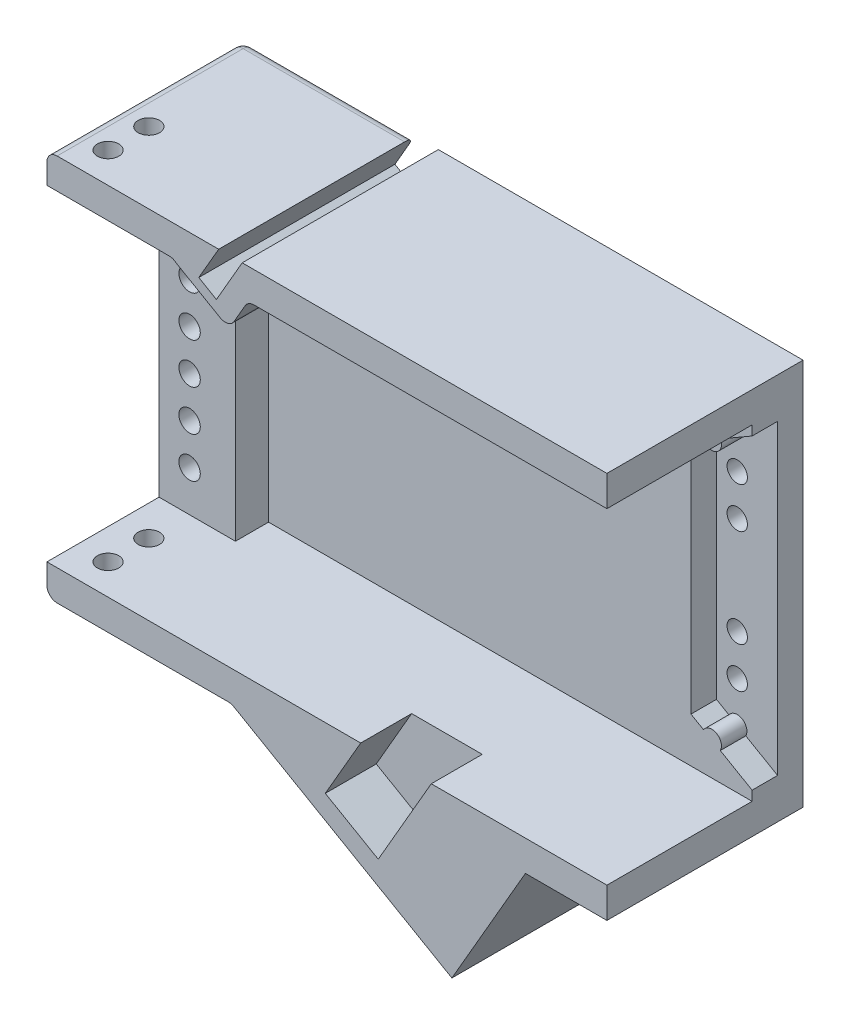
SolidWorks part; units mm, degrees
material "ABS"
ref_plane "前基準面" through (0, 0, 0) normal (0, 0, 1) x (1, 0, 0)
ref_plane "上基準面" through (0, 0, 0) normal (0, 1, 0) x (1, 0, 0)
ref_plane "右基準面" through (0, 0, 0) normal (1, 0, 0) x (0, 0, -1)
sketch "草圖2" plane through (0, 0, 0) normal (0, 0, 1) x (1, 0, 0)
  line L1 (-42.4346, 62.0442) -> (67.4854, 62.0442)
  line L2 (-42.4346, 62.0442) -> (-42.4346, -13.9558)
  line L3 (-42.4346, -13.9558) -> (67.4854, -13.9558)
  line L4 (67.4854, 62.0442) -> (67.4854, -13.9558)
  dimension "D1" = 109.92
  dimension "D2" = 76
extrude "填料-伸長1" add sketch "草圖2" along normal blind 10
sketch "草圖3" plane through (0, 0, 10) normal (0, 0, 1) x (1, 0, 0)
  line L0 (67.4854, 54.1442) -> (67.4854, -6.0558)
  line L1 (67.4854, -13.9558) -> (67.4854, 62.0442) construction
  line L2 (67.4854, 62.0442) -> (-42.4346, 62.0442) construction
  line L3 (67.4854, 54.1442) -> (55.4854, 47.2142)
  line L4 (55.4854, 47.2142) -> (55.4854, 0.8742)
  line L5 (55.4854, 0.8742) -> (67.4854, -6.0558)
  circle A0 centre (59.5654, 49.6442) radius 1.9
  circle A1 centre (59.5654, -1.5558) radius 1.9
  line M6 (67.4854, -13.9558) -> (67.4854, 62.0442)
  dimension "D7" = 7.92
  dimension "D8" = 7.92
  dimension "D9" = 3.8
  dimension "D10" = 3.8
  dimension "D12" = 12.4
  dimension "D1" = 60.2
  dimension "D2" = 7.9
  dimension "D3" = 12
  dimension "D4" = 12
  dimension "D5" = 46.34
  dimension "D6" = 6.93
  dimension "D11" = 51.2
extrude "除料-伸長1" cut sketch "草圖3" against normal blind 5 contours A1 L5 L3 A0 L4 M6
sketch "草圖4" plane through (0, 0, 5) normal (0, 0, 1) x (1, 0, 0)
  line L0 (67.4854, -6.0558) -> (67.4854, 54.1442) construction
  circle A0 centre (59.5654, 41.6442) radius 2
  arc A1 (57.953, 48.6392) -> (61.2418, 50.5385) centre (59.5654, 49.6442) ccw construction
  circle A2 centre (59.5654, 33.6442) radius 2
  circle A3 centre (59.5654, 6.4442) radius 2
  arc A4 (61.2418, -2.4501) -> (57.953, -0.5508) centre (59.5654, -1.5558) ccw construction
  circle A5 centre (59.5654, 14.4442) radius 2
  dimension "D1" = 7.92
  dimension "D2" = 8
  dimension "D3" = 4
  dimension "D5" = 4
  dimension "D6" = 7.92
  dimension "D7" = 8
  dimension "D4" = 2
  dimension "D8" = 2
extrude "除料-伸長2" cut sketch "草圖4" against normal through all
sketch "草圖5" plane through (0, 0, 10) normal (0, 0, 1) x (1, 0, 0)
  line L0 (67.4854, -13.9558) -> (67.4854, -6.0558) construction
  line L1 (-42.4346, -13.9558) -> (67.4854, -13.9558)
  line L2 (-42.4346, -13.9558) -> (-42.4346, -7.9558)
  line L3 (-42.4346, -7.9558) -> (67.4854, -7.9558)
  line L4 (67.4854, -13.9558) -> (67.4854, -7.9558)
  line L5 (-42.4346, 62.0442) -> (-42.4346, -13.9558) construction
  line L6 (67.4854, 62.0442) -> (-42.4346, 62.0442)
  line L7 (67.4854, 62.0442) -> (67.4854, 56.0442)
  line L8 (67.4854, 56.0442) -> (-42.4346, 56.0442)
  line L9 (-42.4346, 62.0442) -> (-42.4346, 56.0442)
  dimension "D1" = 6
  dimension "D2" = 6
extrude "填料-伸長2" add sketch "草圖5" along normal blind 28.5
sketch "草圖6" plane through (0, 0, 10) normal (0, 0, 1) x (1, 0, 0)
  line L0 (67.4854, -7.9558) -> (-42.4346, -7.9558) construction
  line L1 (-42.4346, 56.0442) -> (-27.4346, 56.0442)
  line L2 (-42.4346, 56.0442) -> (-42.4346, -7.9558)
  line L3 (-42.4346, -7.9558) -> (-27.4346, -7.9558)
  line L4 (-27.4346, 56.0442) -> (-27.4346, -7.9558)
  dimension "D1" = 15
extrude "填料-伸長3" add sketch "草圖6" along normal blind 6.5
sketch "草圖7" plane through (0, -7.9558, 0) normal (0, 1, 0) x (1, 0, 0)
  line L0 (67.4854, -10) -> (-27.4346, -10) construction
  line L1 (-42.4346, -38.5) -> (-42.4346, -16.5) construction
  circle A0 centre (-36.4346, -24.5) radius 2.1
  circle A1 centre (-36.4346, -32.5) radius 2.1
  dimension "D1" = 4.2
  dimension "D2" = 14.5
  dimension "D4" = 6
  dimension "D3" = 2
extrude "除料-伸長3" cut sketch "草圖7" against normal through all both and the other way through all
sketch "草圖9" plane through (0, 0, 16.5) normal (0, 0, 1) x (1, 0, 0)
  line L0 (-42.4346, 56.0442) -> (-42.4346, -7.9558) construction
  line L1 (-42.4346, -7.9558) -> (-27.4346, -7.9558) construction
  circle A0 centre (-36.4346, 0.0442) radius 2.1
  circle A1 centre (-36.4346, 8.0442) radius 2.1
  circle A2 centre (-36.4346, 16.0442) radius 2.1
  circle A3 centre (-36.4346, 24.0442) radius 2.1
  circle A4 centre (-36.4346, 32.0442) radius 2.1
  circle A5 centre (-36.4346, 40.0442) radius 2.1
  circle A6 centre (-36.4346, 48.0442) radius 2.1
  dimension "D1" = 6
  dimension "D2" = 4.2
  dimension "D3" = 8
  dimension "D4" = 7
extrude "除料-伸長4" cut sketch "草圖9" against normal through all
sketch "草圖10" plane through (0, 0, 0) normal (0, 0, -1) x (-1, 0, 0)
  line L0 (36.4346, 0.0442) -> (36.4346, 48.0442) construction
  line L1 (32.4346, 0.0442) -> (32.4346, 48.0442)
  line L2 (40.4346, 0.0442) -> (40.4346, 48.0442)
  arc A0 (32.4346, 0.0442) -> (40.4346, 0.0442) centre (36.4346, 0.0442) ccw
  arc A1 (40.4346, 48.0442) -> (32.4346, 48.0442) centre (36.4346, 48.0442) ccw
  point P4 (36.4346, 24.0442)
  dimension "D1" = 8
extrude "除料-伸長5" cut sketch "草圖10" against normal blind 5
sketch "草圖11" plane through (0, 0, 0) normal (0, 0, -1) x (-1, 0, 0)
  line L0 (-51.4854, -13.9558) -> (-37.0517, -38.9558)
  line L1 (42.4346, -13.9558) -> (-67.4854, -13.9558) construction
  line L2 (-37.0517, -38.9558) -> (6.2496, -13.9558)
  line L3 (6.2496, -13.9558) -> (-51.4854, -13.9558)
  line L4 (-51.4854, -13.9558) -> (-67.4854, -13.9558)
  line M15 (-67.4854, -13.9558) -> (42.4346, -13.9558)
  dimension "D1" = 16
  dimension "D2" = 30
  dimension "D3" = 270
  dimension "D4" = 50
extrude "填料-伸長4" add sketch "草圖11" along direction (0, 0, -1) on the side against the normal up to surface (38.5 mm away) contours L0 L2 M15
ref_plane "平面3" through (0, 0, 38.5) normal (0, 0, 1) x (1, 0, 0)
sketch "草圖17" plane through (0, 0, 38.5) normal (0, 0, 1) x (1, 0, 0)
  line L0 (22.5972, -25.9917) -> (12.2049, -19.9917)
  line L1 (22.5972, -25.9917) -> (27.0972, -18.1975)
  line L2 (12.2049, -19.9917) -> (16.7049, -12.1975)
  line L3 (27.0972, -18.1975) -> (16.7049, -12.1975)
  line L4 (-6.2496, -13.9558) -> (37.0517, -38.9558) construction
  line L6 (37.0517, -38.9558) -> (51.4854, -13.9558) construction
  dimension "D1" = 180
  dimension "D2" = 4
  dimension "D3" = 12
  dimension "D4" = 19
  dimension "D5" = 9
extrude "除料-伸長6" cut sketch "草圖17" against normal blind 10
sketch "草圖18" plane through (-1.1055, -1.9147, 0) normal (-0.5, -0.866, 0) x (0.866, -0.5, 0)
  line L1 (32.5656, 28.5) -> (20.5656, 28.5)
  line L2 (32.5656, 28.5) -> (32.5656, 38.5)
  line L3 (32.5656, 38.5) -> (20.5656, 38.5)
  line L4 (20.5656, 28.5) -> (20.5656, 38.5)
extrude "除料-伸長7" cut sketch "草圖18" against normal up to next
sketch "草圖20" plane through (0, 0, 0) normal (0, 0, -1) x (-1, 0, 0)
  line L0 (-0.5128, 62.0442) -> (6.7013, 49.549)
  line L1 (-67.4854, 62.0442) -> (42.4346, 62.0442) construction
  line L2 (6.7013, 49.549) -> (17.0936, 55.549)
  line L3 (17.0936, 55.549) -> (13.3436, 62.0442)
  line L4 (13.3436, 62.0442) -> (-0.5128, 62.0442)
  dimension "D1" = 70
  dimension "D2" = 30
  dimension "D3" = 7.5
  dimension "D4" = 12
extrude "填料-伸長5" add sketch "草圖20" against normal up to surface (38.5 mm away) up to face at (12.5254, 59.0442, 38.5)
sketch "草圖21" plane through (0, 0, 38.5) normal (0, 0, 1) x (1, 0, 0)
  line L0 (-4.106, 62.0442) -> (-8.7248, 62.0442)
  line L1 (67.4854, 62.0442) -> (-42.4346, 62.0442) construction
  line L2 (-8.7248, 62.0442) -> (-12.6295, 55.281)
  line L3 (-12.6295, 55.281) -> (-9.1654, 53.281)
  line L4 (-9.1654, 53.281) -> (-4.106, 62.0442)
  line L5 (-17.0936, 55.549) -> (-6.7013, 49.549) construction
  line L7 (-6.7013, 49.549) -> (-2.9513, 56.0442) construction
  dimension "D1" = 90
  dimension "D2" = 0
  dimension "D3" = 4
  dimension "D4" = 4
  dimension "D5" = 2
extrude "除料-伸長8" cut sketch "草圖21" against normal through all
fillet "圓角1" radius 2 11 edges at (-6.2496, -13.9558, 19.25) (-42.4346, -13.9558, 19.25) (-42.4346, 62.0442, 19.25) (-42.4346, 24.0442, 0) (-24.3421, -13.9558, 0) (15.4011, -26.4558, 0) (-22.1211, 56.0442, 10) (-2.9513, 56.0442, 24.25) (-6.7013, 49.549, 24.25) (-16.8077, 56.0442, 24.25) (-25.5797, 62.0442, 0)
sketch "草圖23" plane through (0, 0, 0) normal (0, 0, -1) x (-1, 0, 0)
  circle A0 centre (-26.9455, -19.8498) radius 1.8
  circle A1 centre (-15.6369, -8.531) radius 1.8
  circle A2 centre (-4.3283, 2.7879) radius 1.8
  circle A3 centre (6.9905, -8.5207) radius 1.8
  dimension "D1" = 3.6
  dimension "D2" = 3.6
  dimension "D3" = 3.6
  dimension "D4" = 3.6
extrude "除料-伸長10" cut sketch "草圖23" against normal blind 8
